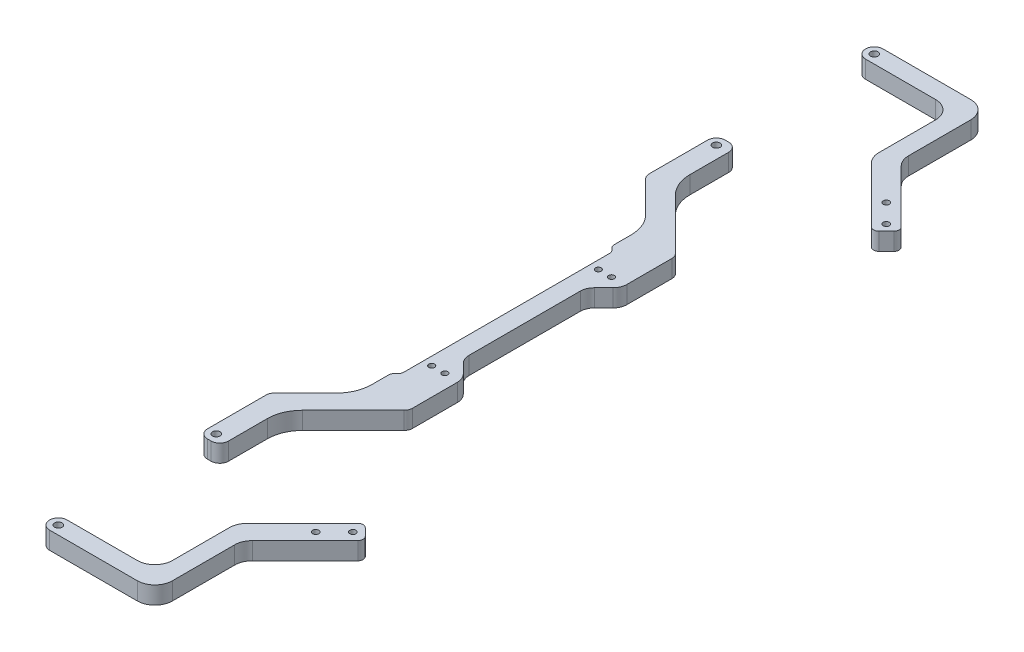
SolidWorks part; units mm, degrees
material "POM 乙缩醛共聚物"
ref_plane "前视基准面" through (0, 0, 0) normal (0, 0, 1) x (1, 0, 0)
ref_plane "上视基准面" through (0, 0, 0) normal (0, 1, 0) x (1, 0, 0)
ref_plane "右视基准面" through (0, 0, 0) normal (1, 0, 0) x (0, 0, -1)
sketch "草图1" plane through (0, 0, 0) normal (0, 1, 0) x (1, 0, 0)
  line L0 (-213.25, 0) -> (213.25, 0) construction
  line L1 (213.25, -47.5) -> (213.25, 47.5) construction
  line L2 (0, -213.25) -> (0, 213.25) construction
  line L3 (-213.25, -47.5) -> (-213.25, 47.5) construction
  line L4 (213.25, 0) -> (221.25, 0) construction
  line L5 (221.25, -67.5) -> (221.25, 67.5)
  line L6 (221.25, 67.5) -> (201.2006, 67.5)
  line L7 (0, 0) -> (180.3122, 180.3122) construction
  line L8 (201.2006, 67.5) -> (67.5, 201.2006)
  line L9 (67.5, 221.25) -> (67.5, 201.2006)
  line L10 (-67.5, 221.25) -> (67.5, 221.25)
  line L11 (-67.5, 221.25) -> (-67.5, 201.2006)
  line L12 (-201.2006, 67.5) -> (-67.5, 201.2006)
  line L13 (-221.25, 67.5) -> (-201.2006, 67.5)
  line L14 (-221.25, -67.5) -> (-221.25, 67.5)
  line L15 (221.25, -67.5) -> (201.2006, -67.5)
  line L16 (201.2006, -67.5) -> (67.5, -201.2006)
  line L17 (67.5, -221.25) -> (67.5, -201.2006)
  line L18 (-221.25, -67.5) -> (-201.2006, -67.5)
  line L19 (-201.2006, -67.5) -> (-67.5, -201.2006)
  line L20 (-67.5, -221.25) -> (-67.5, -201.2006)
  line L21 (-67.5, -221.25) -> (67.5, -221.25)
  circle A0 centre (0, 0) radius 100 construction
  circle A2 centre (0, 0) radius 110
  point P19 (134.3503, 134.3503)
  point P22 (0, 221.25)
  point P31 (-221.25, 0)
  dimension "D1" = 200
  dimension "D4" = 213.25
  dimension "D2" = 213.25
  dimension "D3" = 47.5
  dimension "D5" = 8
  dimension "D6" = 67.5
  dimension "D7" = 10
  dimension "D8" = 255
  dimension "D9" = 65
extrude "凸台-拉伸1" add sketch "草图1" along normal blind 3
sketch "草图2" plane through (0, 3, 0) normal (0, 1, 0) x (1, 0, 0)
  line L0 (0, 0) -> (0, -168) construction
  line L2 (-55, -70) -> (55, -70)
  line L3 (-55, -70) -> (-55, -168)
  line L4 (-55, -168) -> (55, -168)
  line L5 (55, -70) -> (55, -168)
  line L6 (-55, -70) -> (55, -168) construction
  line L7 (-55, -168) -> (55, -70) construction
  point P3 (0, -119)
  dimension "D1" = 168
  dimension "D2" = 110
  dimension "D3" = 98
extrude "切除-拉伸1" cut sketch "草图2" against normal blind 10
sketch "草图3" plane through (0, 3, 0) normal (0, 1, 0) x (1, 0, 0)
  line L0 (55, -168) -> (66, -168)
  line L1 (66, -168) -> (66, -78)
  line L2 (66, -78) -> (55, -78)
  line L3 (55, -78) -> (55, -168)
  dimension "D1" = 11
  dimension "D2" = 90
extrude "切除-拉伸2" cut sketch "草图3" against normal blind 10
sketch "草图4" plane through (0, 3, 0) normal (0, 1, 0) x (1, 0, 0)
  line L0 (-55, -168) -> (66, -168) construction
  line L1 (-4, -153) -> (24, -153)
  line L2 (-4, -153) -> (-4, -183)
  line L3 (-4, -183) -> (24, -183)
  line L4 (24, -153) -> (24, -183)
  line L5 (-4, -153) -> (24, -183) construction
  line L6 (-4, -183) -> (24, -153) construction
  line L7 (0, 0) -> (0, -232.4473) construction
  point P0 (10, -168)
  dimension "D1" = 10
  dimension "D2" = 28
  dimension "D3" = 30
extrude "切除-拉伸3" cut sketch "草图4" against normal blind 10
fillet "圆角1" radius 2 24 edges at (-4, 1.5, 183) (221.25, 1.5, -67.5) (221.25, 1.5, 67.5) (201.2006, 1.5, 67.5) (67.5, 1.5, 201.2006) (67.5, 1.5, 221.25) (-67.5, 1.5, 221.25) (-67.5, 1.5, 201.2006) (-201.2006, 1.5, 67.5) (-221.25, 1.5, 67.5) (-221.25, 1.5, -67.5) (-201.2006, 1.5, -67.5) (-67.5, 1.5, -201.2006) (-67.5, 1.5, -221.25) (67.5, 1.5, -221.25) (67.5, 1.5, -201.2006) (201.2006, 1.5, -67.5) (-55, 1.5, 95.2628) (-55, 1.5, 168) (66, 1.5, 88) (66, 1.5, 168) (-4, 1.5, 168) (24, 1.5, 168) (24, 1.5, 183)
sketch "草图5" plane through (0, 3, 0) normal (0, 1, 0) x (1, 0, 0)
  line L0 (0, 0) -> (-208.25, 0) construction
  line L1 (-208.25, -47.5) -> (-208.25, 47.5) construction
  line L2 (-208.25, 47.5) -> (-197.5, 47.5) construction
  line L3 (-197.5, 47.5) -> (-190, 47.5) construction
  line L4 (-197.5, -47.5) -> (-190, -47.5) construction
  line L5 (-208.25, -47.5) -> (-197.5, -47.5) construction
  line L6 (-47.5, 208.25) -> (47.5, 208.25) construction
  line L7 (0, 208.25) -> (0, 0) construction
  circle A0 centre (-208.25, 47.5) radius 2.65
  circle A1 centre (-197.5, 47.5) radius 1.65
  circle A2 centre (-190, 47.5) radius 1.65
  circle A3 centre (-190, -47.5) radius 1.65
  circle A4 centre (-197.5, -47.5) radius 1.65
  circle A5 centre (-208.25, -47.5) radius 2.65
  circle A24 centre (47.5, 190) radius 1.65
  circle A25 centre (47.5, 197.5) radius 1.65
  circle A26 centre (47.5, 208.25) radius 2.65
  circle A27 centre (-47.5, 208.25) radius 2.65
  circle A28 centre (-47.5, 197.5) radius 1.65
  circle A29 centre (-47.5, 190) radius 1.65
  circle A30 centre (190, -47.5) radius 1.65
  circle A31 centre (197.5, -47.5) radius 1.65
  circle A32 centre (208.25, -47.5) radius 2.65
  circle A33 centre (208.25, 47.5) radius 2.65
  circle A34 centre (197.5, 47.5) radius 1.65
  circle A35 centre (190, 47.5) radius 1.65
  circle A36 centre (-47.5, -190) radius 1.65
  circle A37 centre (-47.5, -197.5) radius 1.65
  circle A38 centre (-47.5, -208.25) radius 2.65
  circle A39 centre (47.5, -208.25) radius 2.65
  circle A40 centre (47.5, -197.5) radius 1.65
  circle A41 centre (47.5, -190) radius 1.65
  point P55 (1.5152, 1.5152)
  dimension "D2" = 5.3
  dimension "D4" = 7.5
  dimension "D5" = 3.3
  dimension "D7" = 95
  dimension "D1" = 208.25
  dimension "D3" = 10.75
  dimension "D6" = 4
extrude "切除-拉伸4" cut sketch "草图5" against normal blind 10
sketch "草图6" plane through (0, 3, 0) normal (0, 1, 0) x (1, 0, 0)
  line L0 (0, 0) -> (0, -221.25) construction
  line L1 (-65.5, -221.25) -> (65.5, -221.25) construction
  line L2 (67.5, -219.25) -> (67.5, -202.029) construction
  line L3 (-67.5, -237.25) -> (67.5, -237.25)
  line L4 (-67.5, -237.25) -> (-67.5, -205.25)
  line L5 (-67.5, -205.25) -> (67.5, -205.25)
  line L6 (67.5, -237.25) -> (67.5, -205.25)
  line L7 (-67.5, -237.25) -> (67.5, -205.25) construction
  line L8 (-67.5, -205.25) -> (67.5, -237.25) construction
  line L9 (-237.25, 67.5) -> (-237.25, -67.5)
  line L10 (-237.25, 67.5) -> (-205.25, 67.5)
  line L11 (-237.25, -67.5) -> (-205.25, -67.5)
  line L12 (-205.25, 67.5) -> (-205.25, -67.5)
  line L21 (-237.25, 67.5) -> (-205.25, -67.5) construction
  line L23 (67.5, 237.25) -> (-67.5, 237.25) [skipped]
  line L24 (67.5, 237.25) -> (67.5, 205.25) [skipped]
  line L25 (-67.5, 237.25) -> (-67.5, 205.25) [skipped]
  line L26 (67.5, 205.25) -> (-67.5, 205.25) [skipped]
  line L27 (237.25, -67.5) -> (237.25, 67.5) [skipped]
  line L28 (237.25, -67.5) -> (205.25, -67.5) [skipped]
  line L29 (237.25, 67.5) -> (205.25, 67.5) [skipped]
  line L30 (205.25, -67.5) -> (205.25, 67.5) [skipped]
  line L34 (237.25, 67.5) -> (205.25, 67.5)
  line L35 (205.25, 67.5) -> (205.25, -67.5)
  line L36 (237.25, -67.5) -> (205.25, -67.5)
  line L37 (237.25, 67.5) -> (237.25, -67.5)
  line L38 (-221.25, 0) -> (0, 0) construction
  line L39 (-219.5626, -92.2876) -> (-219.5626, -92.9346) construction
  line L40 (-67.5, 205.25) -> (67.5, 205.25)
  line L41 (-205.25, 67.5) -> (-237.25, -67.5) construction
  line L42 (67.5, 237.25) -> (67.5, 205.25)
  line L43 (-67.5, 237.25) -> (67.5, 237.25)
  line L44 (-67.5, 237.25) -> (-67.5, 205.25)
  point P26 (0, 0)
  dimension "D1" = 16
  dimension "D2" = 4
extrude "切除-拉伸5" cut sketch "草图6" against normal through all
sketch "草图7" plane through (0, 3, 0) normal (0, 1, 0) x (1, 0, 0)
  line L0 (0, 0) -> (169.5, 0) construction
  line L3 (140.5, 65) -> (169.5, 65)
  line L4 (140.5, 65) -> (140.5, -65)
  line L5 (140.5, -65) -> (169.5, -65)
  line L6 (169.5, 65) -> (169.5, -65)
  line L7 (140.5, 65) -> (169.5, -65) construction
  line L8 (140.5, -65) -> (169.5, 65) construction
  point P5 (155, 0)
  dimension "D1" = 130
  dimension "D2" = 29
  dimension "D3" = 155
extrude "切除-拉伸6" cut sketch "草图7" against normal blind 10
sketch "草图8" plane through (0, 3, 0) normal (0, 1, 0) x (1, 0, 0)
  line L0 (0, 0) -> (134.3503, -134.3503) construction
  line L1 (68.0858, -200.6148) -> (200.6148, -68.0858) construction
  line L2 (134.3503, -134.3503) -> (162.6346, -162.6346) construction
  line L3 (110.6622, -214.6069) -> (214.6069, -110.6622)
  line L4 (214.6069, -110.6622) -> (199.5118, -69.1888)
  line L5 (110.6622, -214.6069) -> (69.1888, -199.5118)
  line L6 (199.5118, -69.1888) -> (69.1888, -199.5118)
  line L7 (0, 0) -> (252.2182, 0) construction
  line L8 (0, 0) -> (0, -92.3729) construction
  line L9 (214.6069, 110.6622) -> (199.5118, 69.1888)
  line L10 (110.6622, 214.6069) -> (214.6069, 110.6622)
  line L11 (110.6622, 214.6069) -> (69.1888, 199.5118)
  line L12 (199.5118, 69.1888) -> (69.1888, 199.5118)
  line L13 (-214.6069, -110.6622) -> (-199.5118, -69.1888)
  line L14 (-110.6622, -214.6069) -> (-214.6069, -110.6622)
  line L15 (-110.6622, -214.6069) -> (-69.1888, -199.5118)
  line L16 (-199.5118, -69.1888) -> (-69.1888, -199.5118)
  line L17 (-110.6622, 214.6069) -> (-214.6069, 110.6622)
  line L18 (-110.6622, 214.6069) -> (-69.1888, 199.5118)
  line L19 (-199.5118, 69.1888) -> (-69.1888, 199.5118)
  line L20 (-214.6069, 110.6622) -> (-199.5118, 69.1888)
  dimension "D1" = 40
  dimension "D2" = 73.5
  dimension "D3" = 115
extrude "凸台-拉伸2" add sketch "草图8" against normal up to surface (3 mm away) up to face at (155, 0, 0)
ref_plane "基准面1" through (0, 0, 0) normal (-0.7071, 0, 0.7071) x (0.7071, 0, 0.7071)
sketch "草图12" plane through (0, 3, 0) normal (0, 1, 0) x (1, 0, 0)
  line L0 (0, 0) -> (162.6346, -162.6346) construction
  line L1 (110.6622, -214.6069) -> (214.6069, -110.6622) construction
  line L2 (155.5635, -155.5635) -> (162.6346, -148.4924) construction
  line L3 (162.6346, -148.4924) -> (152.028, -137.8858) construction
  line L4 (0, 0) -> (24.1105, 24.1105) construction
  line L5 (0, 0) -> (252.2182, 0) construction
  line L6 (162.6346, 148.4924) -> (152.028, 137.8858) construction
  line L7 (252.2182, -23.8295) -> (253.2892, -23.8295) construction
  line L8 (0, 0) -> (0, 85.4115) construction
  line L9 (155.5635, 155.5635) -> (162.6346, 148.4924) construction
  line L10 (-162.6346, -148.4924) -> (-152.028, -137.8858) construction
  line L11 (-155.5635, -155.5635) -> (-162.6346, -148.4924) construction
  line L12 (0, 0) -> (-162.6346, -162.6346) construction
  line L13 (-155.5635, 155.5635) -> (-162.6346, 148.4924) construction
  line L14 (-162.6346, 148.4924) -> (-152.028, 137.8858) construction
  circle A0 centre (162.6346, -148.4924) radius 1.65
  circle A1 centre (152.028, -137.8858) radius 1.65
  circle A2 centre (137.8858, -152.028) radius 1.65
  circle A3 centre (148.4924, -162.6346) radius 1.65
  circle A4 centre (148.4924, 162.6346) radius 1.65
  circle A5 centre (137.8858, 152.028) radius 1.65
  circle A6 centre (152.028, 137.8858) radius 1.65
  circle A7 centre (162.6346, 148.4924) radius 1.65
  circle A8 centre (-148.4924, -162.6346) radius 1.65
  circle A9 centre (-137.8858, -152.028) radius 1.65
  circle A10 centre (-152.028, -137.8858) radius 1.65
  circle A11 centre (-162.6346, -148.4924) radius 1.65
  circle A12 centre (-162.6346, 148.4924) radius 1.65
  circle A13 centre (-152.028, 137.8858) radius 1.65
  circle A14 centre (-137.8858, 152.028) radius 1.65
  circle A15 centre (-148.4924, 162.6346) radius 1.65
  dimension "D1" = 3.3
  dimension "D2" = 3.3
  dimension "D3" = 15
  dimension "D4" = 20
  dimension "D5" = 205
extrude "切除-拉伸7" cut sketch "草图12" against normal blind 112
sketch "草图13" plane through (0, 3, 0) normal (0, 1, 0) x (1, 0, 0)
  line L0 (-205.25, 0) -> (205.25, 0)
  line L1 (-205.25, -67.5) -> (-205.25, 67.5) construction
  line L2 (205.25, 67.5) -> (205.25, -67.5) construction
extrude "切除-拉伸-薄壁1" cut sketch "草图13" against normal through all both and the other way through all thin thin type mid plane wall 2
sketch "草图14" plane through (0, 3, 0) normal (0, 1, 0) x (1, 0, 0)
  line L0 (0, 205.25) -> (0, -205.25)
  line L1 (-67.5, 205.25) -> (67.5, 205.25) construction
  line L2 (67.5, -205.25) -> (-67.5, -205.25) construction
extrude "切除-拉伸-薄壁2" cut sketch "草图14" against normal through all and the other way through all thin thin type mid plane wall 2
fillet "圆角2" radius 3 8 edges at (-1, 1.5, 205.25) (-69.1888, 1.5, 199.5118) (-67.5, 1.5, 205.25) (-205.25, 1.5, 1) (-199.5118, 1.5, 69.1888) (-205.25, 1.5, 67.5) (-214.6069, 1.5, 110.6622) (-110.6622, 1.5, 214.6069)
fillet "圆角3" radius 3 14 edges at (169.5, 1.5, 65) (140.5, 1.5, 65) (109.9955, 1.5, 1) (140.5, 1.5, 1) (169.5, 1.5, 1) (205.25, 1.5, 1) (205.25, 1.5, 67.5) (199.5118, 1.5, 69.1888) (214.6069, 1.5, 110.6622) (110.6622, 1.5, 214.6069) (69.1888, 1.5, 199.5118) (67.5, 1.5, 205.25) (1, 1.5, 183) (1, 1.5, 205.25)
fillet "圆角4" radius 3 13 edges at (1, 1.5, -109.9955) (1, 1.5, -205.25) (69.1888, 1.5, -199.5118) (67.5, 1.5, -205.25) (110.6622, 1.5, -214.6069) (214.6069, 1.5, -110.6622) (205.25, 1.5, -67.5) (169.5, 1.5, -65) (140.5, 1.5, -65) (109.9955, 1.5, -1) (140.5, 1.5, -1) (169.5, 1.5, -1) (205.25, 1.5, -1)
fillet "圆角5" radius 3 10 edges at (-67.5, 1.5, -205.25) (-69.1888, 1.5, -199.5118) (-110.6622, 1.5, -214.6069) (-214.6069, 1.5, -110.6622) (-199.5118, 1.5, -69.1888) (-205.25, 1.5, -67.5) (-205.25, 1.5, -1) (-109.9955, 1.5, -1) (-1, 1.5, -109.9955) (-1, 1.5, -205.25)
fillet "圆角6" radius 3 2 edges at (-1, 1.5, 183) (-109.9955, 1.5, 1)
sketch "草图15" plane through (0, 0, 0) normal (0, -1, 0) x (1, 0, 0)
  line L0 (148.4924, -162.6346) -> (106.066, -205.061) construction
  line L1 (162.6346, -162.6346) -> (105.0927, -105.0927) construction
  line L2 (112.0136, -213.2555) -> (213.2555, -112.0136) construction
  line L3 (162.6346, -162.6346) -> (213.2555, -112.0136) construction
  line L4 (106.066, -205.061) -> (91.9239, -190.9188) construction
  line L5 (205.061, -106.066) -> (190.9188, -91.9239) construction
  line L6 (162.6346, -148.4924) -> (205.061, -106.066) construction
  line L7 (0, 0) -> (248.6294, 0) construction
  line L8 (0, 0) -> (0, -244.0653) construction
  line L9 (-162.6346, -148.4924) -> (-205.061, -106.066) construction
  line L10 (-205.061, -106.066) -> (-190.9188, -91.9239) construction
  line L11 (-106.066, -205.061) -> (-91.9239, -190.9188) construction
  line L12 (-162.6346, -162.6346) -> (-213.2555, -112.0136) construction
  line L13 (-162.6346, -162.6346) -> (-105.0927, -105.0927) construction
  line L14 (-148.4924, -162.6346) -> (-106.066, -205.061) construction
  line L15 (-148.4924, 162.6346) -> (-106.066, 205.061) construction
  line L16 (-162.6346, 162.6346) -> (-105.0927, 105.0927) construction
  line L17 (-162.6346, 162.6346) -> (-213.2555, 112.0136) construction
  line L18 (-106.066, 205.061) -> (-91.9239, 190.9188) construction
  line L19 (-205.061, 106.066) -> (-190.9188, 91.9239) construction
  line L20 (-162.6346, 148.4924) -> (-205.061, 106.066) construction
  line L21 (162.6346, 148.4924) -> (205.061, 106.066) construction
  line L22 (205.061, 106.066) -> (190.9188, 91.9239) construction
  line L23 (106.066, 205.061) -> (91.9239, 190.9188) construction
  line L24 (162.6346, 162.6346) -> (213.2555, 112.0136) construction
  line L25 (162.6346, 162.6346) -> (105.0927, 105.0927) construction
  line L26 (148.4924, 162.6346) -> (106.066, 205.061) construction
  circle A0 centre (106.066, -205.061) radius 1.75
  circle A1 centre (91.9239, -190.9188) radius 1.75
  circle A2 centre (190.9188, -91.9239) radius 1.75
  circle A3 centre (205.061, -106.066) radius 1.75
  circle A4 centre (-205.061, -106.066) radius 1.75
  circle A5 centre (-190.9188, -91.9239) radius 1.75
  circle A6 centre (-91.9239, -190.9188) radius 1.75
  circle A7 centre (-106.066, -205.061) radius 1.75
  circle A8 centre (-106.066, 205.061) radius 1.75
  circle A9 centre (-91.9239, 190.9188) radius 1.75
  circle A10 centre (-190.9188, 91.9239) radius 1.75
  circle A11 centre (-205.061, 106.066) radius 1.75
  circle A12 centre (205.061, 106.066) radius 1.75
  circle A13 centre (190.9188, 91.9239) radius 1.75
  circle A14 centre (91.9239, 190.9188) radius 1.75
  circle A15 centre (106.066, 205.061) radius 1.75
  dimension "D2" = 3.5
  dimension "D4" = 3.5
  dimension "D1" = 140
  dimension "D3" = 20
extrude "切除-拉伸8" cut sketch "草图15" against normal blind 10
sketch "草图16" plane through (0, 3, 0) normal (0, 1, 0) x (1, 0, 0)
  line L0 (0, 0) -> (-162.6346, 162.6346) construction
  line L1 (-112.0136, 213.2555) -> (-213.2555, 112.0136) construction
  line L2 (-134.3503, 134.3503) -> (-118.7939, 149.9066) construction
  line L3 (-94.7523, 94.7523) -> (-71.7713, 117.7333) construction
  circle A0 centre (-118.7939, 149.9066) radius 1.65
  circle A1 centre (-71.7713, 117.7333) radius 2.15
  circle A2 centre (-117.7333, 71.7713) radius 2.15
  circle A3 centre (-149.9066, 118.7939) radius 1.65
  dimension "D3" = 3.3
  dimension "D4" = 4.3
  dimension "D5" = 65
  dimension "D6" = 56
  dimension "D1" = 22
  dimension "D2" = 190
extrude "切除-拉伸9" cut sketch "草图16" against normal blind 10
sketch "草图18" plane through (0, 3, 0) normal (0, 1, 0) x (1, 0, 0)
  line L0 (0, 0) -> (-264.5947, 0) construction
  line L1 (-268.4627, 195) -> (-239.3639, 195) construction
  line L2 (-182, -75.934) -> (-182, 75.934)
  line L3 (-182, 75.934) -> (-218.25, 112.184)
  line L4 (-218.25, 112.184) -> (-218.25, 188.3799)
  line L5 (-205.25, 4) -> (-205.25, 64.5) construction
  line L6 (0, 0) -> (-162.6346, 162.6346) construction
  line L7 (-112.0136, 213.2555) -> (-213.2555, 112.0136) construction
  line L8 (-213.1287, 190.5013) -> (-152.7351, 130.1076)
  line L9 (-205.25, -82.2134) -> (-205.25, 82.2134)
  line L10 (-205.25, 82.2134) -> (-230.25, 107.2134)
  line L11 (-230.25, 107.2134) -> (-230.25, 212.5221)
  line L12 (-221.7145, 216.0576) -> (-144.2498, 138.5929)
  line L13 (-144.2498, 138.5929) -> (-152.7351, 130.1076)
  line L15 (-268.4627, -195) -> (-227.2747, -195) construction
  line L16 (-144.2498, -138.5929) -> (-152.7351, -130.1076)
  line L17 (-221.7145, -216.0576) -> (-144.2498, -138.5929)
  line L18 (-230.25, -107.2134) -> (-230.25, -212.5221)
  line L19 (-205.25, -82.2134) -> (-230.25, -107.2134)
  line L20 (-213.1287, -190.5013) -> (-152.7351, -130.1076)
  line L21 (-218.25, -112.184) -> (-218.25, -188.3799)
  line L22 (-182, -75.934) -> (-218.25, -112.184)
  line L23 (-148.4924, 134.3503) -> (-152.028, 137.8858) construction
  circle A0 centre (-190, 47.5) radius 1.65 construction
  circle A1 centre (-197.5, 47.5) radius 1.65 construction
  circle A2 centre (-197.5, -47.5) radius 1.65 construction
  circle A3 centre (-190, -47.5) radius 1.65 construction
  circle A4 centre (-190, 47.5) radius 1.65
  circle A5 centre (-197.5, 47.5) radius 1.65
  circle A6 centre (-197.5, -47.5) radius 1.65
  circle A7 centre (-190, -47.5) radius 1.65
  circle A8 centre (-190.9188, 91.9239) radius 1.75 construction
  arc A9 (-230.25, 212.5221) -> (-221.7145, 216.0576) centre (-225.25, 212.5221) cw
  arc A11 (-218.25, 188.3799) -> (-213.1287, 190.5013) centre (-215.25, 188.3799) cw
  circle A12 centre (-152.028, 137.8858) radius 1.65 construction
  arc A13 (-218.25, -188.3799) -> (-213.1287, -190.5013) centre (-215.25, -188.3799) ccw
  arc A14 (-230.25, -212.5221) -> (-221.7145, -216.0576) centre (-225.25, -212.5221) ccw
  circle A15 centre (-197.5, -47.5) radius 1.65
  circle A16 centre (-190, -47.5) radius 1.65
  circle A24 centre (-152.028, -137.8858) radius 1.65
  circle A25 centre (-162.6346, -148.4924) radius 1.65
  circle A28 centre (-152.028, -137.8858) radius 1.65 construction
  circle A30 centre (-152.028, 137.8858) radius 1.65
  circle A31 centre (-162.6346, -148.4924) radius 1.65 construction
  circle A32 centre (-162.6346, 148.4924) radius 1.65
  point P58 (-205.25, 0)
  point P60 (-182, 0)
  dimension "D3" = 8
  dimension "D9" = 5
  dimension "D10" = 3
  dimension "D11" = 5
  dimension "D1" = 195
  dimension "D2" = 13
  dimension "D4" = 5
  dimension "D6" = 12
  dimension "D7" = 12
  dimension "D8" = 12
extrude "凸台-拉伸3" add sketch "草图18" along normal blind 10
sketch "草图19" plane through (-205.25, 0, 0) normal (-1, 0, 0) x (0, 0, 1)
  line L0 (-245.4596, 3) -> (284.5404, 3)
  line L1 (159.8061, 3) -> (213.2555, 3) construction
  line L2 (284.5404, 3) -> (284.5404, -37)
  line L3 (284.5404, -37) -> (-245.4596, -37)
  line L4 (-245.4596, -37) -> (-245.4596, 3)
  dimension "D1" = 40
  dimension "D2" = 530
  dimension "D3" = 246.4596
extrude "切除-拉伸10" cut sketch "草图19" against normal through all both and the other way through all
sketch "草图20" plane through (0, 13, 0) normal (0, 1, 0) x (1, 0, 0)
  circle A0 centre (-152.028, 137.8858) radius 1.65 construction
  circle A1 centre (-162.6346, 148.4924) radius 1.65 construction
  circle A2 centre (-152.028, 137.8858) radius 1.65
  circle A3 centre (-162.6346, 148.4924) radius 1.65
extrude "凸台-拉伸4" add sketch "草图20" against normal up to surface (10 mm away) up to face at (-201.7968, 3, 0)
sketch "草图23" plane through (0, 13, 0) normal (0, 1, 0) x (1, 0, 0)
  line L0 (-225.25, 217.5221) -> (-175.25, 217.5221)
  line L1 (-165.25, 207.5221) -> (-165.25, 159.5931)
  line L2 (-221.7145, 216.0576) -> (-144.2498, 138.5929) construction
  line L3 (-175.25, 169.5931) -> (-175.25, 197.5221)
  line L4 (-185.25, 207.5221) -> (-213.1789, 207.5221)
  line L5 (-221.7145, 216.0576) -> (-213.1789, 207.5221)
  line L6 (-175.25, 169.5931) -> (-165.25, 159.5931)
  line L7 (-175.25, 169.5931) -> (-144.2498, 138.5929)
  arc A0 (-221.7145, 216.0576) -> (-230.25, 212.5221) centre (-225.25, 212.5221) ccw construction
  arc A1 (-221.7145, 216.0576) -> (-225.25, 217.5221) centre (-225.25, 212.5221) ccw
  arc A2 (-175.25, 217.5221) -> (-165.25, 207.5221) centre (-175.25, 207.5221) cw
  arc A3 (-175.25, 197.5221) -> (-185.25, 207.5221) centre (-185.25, 197.5221) ccw
  point P10 (-165.25, 217.5221)
  line M27 (-144.2498, 138.5929) -> (-221.7145, 216.0576)
  arc M28 (-221.7145, 216.0576) -> (-230.25, 212.5221) centre (-225.25, 212.5221) ccw
  dimension "D4" = 10
  dimension "D1" = 10
  dimension "D2" = 60
  dimension "D3" = 10
extrude "凸台-拉伸6" add sketch "草图23" against normal blind 10 contours A3 L3 L1 A2 L0 L4 M27 M28
sketch "草图24" plane through (0, 3, 0) normal (0, -1, 0) x (1, 0, 0)
  line L0 (-218.25, -188.3799) -> (-218.25, -207.5221)
  line L1 (-218.25, -207.5221) -> (-213.1789, -207.5221)
  line L2 (-213.1789, -207.5221) -> (-175.25, -169.5931)
  line L3 (-175.25, -169.5931) -> (-175.25, -152.6226)
  line L4 (-213.1287, -190.5013) -> (-152.7351, -130.1076) construction
  line L5 (-175.25, -152.6226) -> (-218.25, -188.3799)
  line L6 (-185.25, -207.5221) -> (-213.1789, -207.5221) construction
extrude "切除-拉伸12" cut sketch "草图24" against normal through all
mirror "镜向1" about plane through (0, 0, 0) normal (0, 0, 1) of "切除-拉伸12", "凸台-拉伸6"
fillet "圆角7" radius 5 2 edges at (-218.25, 8, -207.5221) (-218.25, 8, 207.5221)
fillet "圆角8" radius 5 10 edges at (-152.7351, 8, 130.1076) (-144.2498, 8, 138.5929) (-230.25, 8, 107.2134) (-230.25, 8, -107.2134) (-144.2498, 8, -138.5929) (-152.7351, 8, -130.1076) (-182, 8, -75.934) (-182, 8, 75.934) (-175.25, 8, 152.6226) (-175.25, 8, -152.6226)
sketch "草图25" plane through (0, 13, 0) normal (0, 1, 0) x (1, 0, 0)
  line L0 (0, 0) -> (-287.1356, 0) construction
  circle A0 centre (-152.028, 137.8858) radius 1.65
  circle A1 centre (-162.6346, 148.4924) radius 1.65
  circle A2 centre (-152.028, -137.8858) radius 1.65 construction
  circle A3 centre (-162.6346, -148.4924) radius 1.65 construction
extrude "切除-拉伸13" cut sketch "草图25" against normal through all
sketch "草图26" plane through (0, 13, 0) normal (0, 1, 0) x (1, 0, 0)
  line L0 (0, 0) -> (-220.6337, 0) construction
  line L1 (0, 0) -> (-174.267, 174.267) construction
  line L2 (-152.028, 137.8858) -> (-144.9569, 144.9569) construction
  line L3 (-144.9569, 144.9569) -> (-137.8858, 152.028) construction
  line L4 (-137.8858, 152.028) -> (-148.4924, 162.6346) construction
  line L5 (-140.7142, 146.3711) -> (-165.25, 170.9069)
  line L6 (-165.25, 207.5221) -> (-165.25, 159.5931) construction
  line L7 (-136.4716, 146.3711) -> (-132.229, 150.6137)
  line L8 (-132.229, 154.8564) -> (-165.25, 187.8774)
  line L9 (-165.25, 159.5931) -> (-147.7853, 142.1285) construction
  line L10 (-173.7855, 151.1581) -> (-156.2706, 133.6432) construction
  line L11 (-165.25, 187.8774) -> (-165.25, 170.9069)
  line L12 (-132.229, -154.8564) -> (-165.25, -187.8774)
  line L13 (-136.4716, -146.3711) -> (-132.229, -150.6137)
  line L14 (-140.7142, -146.3711) -> (-165.25, -170.9069)
  line L15 (-165.25, -187.8774) -> (-165.25, -170.9069)
  line L16 (-137.8858, -152.028) -> (-148.4924, -162.6346) construction
  line L17 (-144.9569, -144.9569) -> (-137.8858, -152.028) construction
  circle A0 centre (-137.8858, 152.028) radius 1.75
  circle A1 centre (-148.4924, 162.6346) radius 1.75
  arc A2 (-132.229, 150.6137) -> (-132.229, 154.8564) centre (-134.3503, 152.7351) ccw
  arc A3 (-140.7142, 146.3711) -> (-136.4716, 146.3711) centre (-138.5929, 148.4924) ccw
  arc A4 (-132.229, -150.6137) -> (-132.229, -154.8564) centre (-134.3503, -152.7351) cw
  arc A5 (-140.7142, -146.3711) -> (-136.4716, -146.3711) centre (-138.5929, -148.4924) cw
  circle A6 centre (-148.4924, -162.6346) radius 1.75
  circle A7 centre (-137.8858, -152.028) radius 1.75
  dimension "D3" = 3.5
  dimension "D5" = 3.5
  dimension "D7" = 3
  dimension "D1" = 45
  dimension "D2" = 10
  dimension "D4" = 15
  dimension "D6" = 5
extrude "凸台-拉伸7" add sketch "草图26" against normal up to surface (10 mm away) up to face at (-152.028, 3, -136.2358)
sketch "草图27" plane through (0, 13, 0) normal (0, 1, 0) x (1, 0, 0)
  line L0 (0, 0) -> (-205.25, 0) construction
  line L1 (-205.25, -82.2134) -> (-205.25, 82.2134) construction
  line L2 (-165.25, 170.9069) -> (-175.25, 180.9069)
  line L3 (-175.25, 154.6937) -> (-175.25, 197.5221) construction
  line L4 (-175.25, 180.9069) -> (-175.25, 129.5435)
  line L5 (-175.25, 129.5435) -> (-140.7781, 129.5435)
  line L6 (-140.7781, 129.5435) -> (-140.7142, 146.3711)
  line L7 (-140.7142, 146.3711) -> (-165.25, 170.9069)
  line L8 (-140.7142, -146.3711) -> (-165.25, -170.9069)
  line L9 (-140.7781, -129.5435) -> (-140.7142, -146.3711)
  line L10 (-175.25, -129.5435) -> (-140.7781, -129.5435)
  line L11 (-175.25, -180.9069) -> (-175.25, -129.5435)
  line L12 (-165.25, -170.9069) -> (-175.25, -180.9069)
  dimension "D1" = 16.8276
  dimension "D2" = 34.4719
extrude "切除-拉伸14" cut sketch "草图27" against normal blind 10
fillet "圆角9" radius 10 4 edges at (-165.25, 8, 187.8774) (-175.25, 8, 180.9069) (-165.25, 8, -187.8774) (-175.25, 8, -180.9069)
fillet "圆角13" radius 20 2 edges at (-218.25, 8, 112.184) (-205.25, 8, 82.2134)
fillet "圆角14" radius 20 2 edges at (-218.25, 8, -112.184) (-205.25, 8, -82.2134)
sketch "草图30" plane through (0, 3, 0) normal (0, -1, 0) x (1, 0, 0)
  line L0 (-205.25, 0) -> (-173.7724, 0) construction
  line L1 (-205.25, 73.9291) -> (-205.25, -73.9291) construction
  line L2 (-182, 45) -> (-192, 35)
  line L3 (-182, 73.8629) -> (-182, -73.8629) construction
  line L4 (-192, 35) -> (-192, -35)
  line L5 (-182, 45) -> (-182, -45)
  line L6 (-182, -45) -> (-192, -35)
  point P12 (-182, 0)
  point P13 (-192, 0)
  dimension "D1" = 45
  dimension "D2" = 35
  dimension "D3" = 10
extrude "切除-拉伸16" cut sketch "草图30" against normal through all
fillet "圆角15" radius 8 4 edges at (-182, 8, 45) (-182, 8, -45) (-192, 8, -35) (-192, 8, 35)
sketch "草图31" plane through (0, 3, 0) normal (0, -1, 0) x (1, 0, 0)
  line L0 (-205.25, 0) -> (-236.4193, 0) construction
  line L1 (-205.25, 73.9291) -> (-205.25, -73.9291) construction
  line L2 (-205.25, 63) -> (-202.25, 60)
  line L3 (-202.25, 60) -> (-202.25, 0)
  line L4 (-205.25, 63) -> (-205.25, -63)
  line L5 (-205.25, -63) -> (-202.25, -60)
  line L6 (-202.25, -60) -> (-202.25, 0)
  dimension "D1" = 135
  dimension "D2" = 60
  dimension "D3" = 3
extrude "切除-拉伸17" cut sketch "草图31" against normal through all
fillet "圆角16" radius 3 4 edges at (-205.25, 8, -63) (-205.25, 8, 63) (-202.25, 8, 60) (-202.25, 8, -60)
sketch "草图32" plane through (0, 3, 0) normal (0, -1, 0) x (1, 0, 0)
  line L0 (0, 0) -> (-270.1642, 0) construction
  line L1 (-213.25, 207.5221) -> (-230.25, 207.5221)
  line L2 (-230.25, 109.2845) -> (-230.25, 212.5221) construction
  line L3 (-213.25, 207.5221) -> (-213.25, 147.5221)
  line L4 (-213.25, 147.5221) -> (-230.25, 147.5221)
  line L5 (-230.25, 207.5221) -> (-230.25, 147.5221)
  line L6 (-230.25, -207.5221) -> (-230.25, -147.5221)
  line L7 (-213.25, -147.5221) -> (-230.25, -147.5221)
  line L8 (-213.25, -207.5221) -> (-213.25, -147.5221)
  line L9 (-213.25, -207.5221) -> (-230.25, -207.5221)
  dimension "D1" = 60
extrude "切除-拉伸18" cut sketch "草图32" against normal through all
fillet "圆角17" radius 5 3 edges at (-230.25, 13, 210.0221) (-230.25, 8, 207.5221) (-230.25, 3, 210.0221)
fillet "圆角18" radius 5 4 edges at (-230.25, 8, 147.5221) (-230.25, 8, -147.5221) (-218.25, 8, -147.5221) (-218.25, 8, 147.5221)
fillet "圆角19" radius 5 1 edges at (-230.25, 8, -207.5221)
sketch "草图33" plane through (0, 13, 0) normal (0, 1, 0) x (1, 0, 0)
  line L0 (-225.25, -212.5221) -> (-225.25, 228.6741) construction
  line L1 (-192, 0) -> (-297.6492, 0) construction
  line L2 (-192, -31.6863) -> (-192, 31.6863) construction
  circle A0 centre (-225.25, -212.5221) radius 2.15
  circle A1 centre (-225.25, -142.5221) radius 2.15
  circle A2 centre (-225.25, 212.5221) radius 2.15
  circle A3 centre (-225.25, 142.5221) radius 2.15
  dimension "D1" = 4.3
  dimension "D2" = 70
extrude "切除-拉伸19" cut sketch "草图33" against normal through all
sketch "草图34" plane through (0, 13, 0) normal (0, 1, 0) x (1, 0, 0)
  line L0 (-225.25, 212.5221) -> (-174.3723, 212.5221) construction
  line L1 (-175.25, 192.0196) -> (-165.25, 192.0196)
  line L2 (0, 0) -> (-388.6241, 0) construction
  line L3 (-175.25, -217.5221) -> (-225.25, -217.5221) construction
  line L4 (-225.25, -207.5221) -> (-185.25, -207.5221) construction
  line L5 (-225.25, -232.5221) -> (-174.3723, -232.5221) construction
  line L6 (-225.25, -212.5221) -> (-174.3723, -212.5221) construction
  line L7 (-165.25, -192.0196) -> (-165.25, -227.5221)
  line L8 (-225.25, 232.5221) -> (-174.3723, 232.5221) construction
  line L9 (-175.25, 237.5221) -> (-225.25, 237.5221)
  line L10 (-225.25, 227.5221) -> (-185.25, 227.5221)
  line L11 (-225.25, 227.5221) -> (-185.25, 227.5221) construction
  line L12 (-136.4716, -146.3711) -> (-132.229, -150.6137)
  line L13 (-175.25, -217.5221) -> (-175.25, -192.0196)
  line L14 (-225.25, -227.5221) -> (-185.25, -227.5221)
  line L15 (-175.25, -237.5221) -> (-225.25, -237.5221)
  line L16 (-225.25, 207.5221) -> (-185.25, 207.5221)
  line L17 (-175.25, 197.5221) -> (-175.25, 185.049)
  line L18 (-172.3211, 177.9779) -> (-140.7142, 146.3711)
  line L19 (-136.4716, 146.3711) -> (-132.229, 150.6137)
  line L20 (-132.229, 154.8564) -> (-162.3211, 184.9485)
  line L21 (-165.25, 192.0196) -> (-165.25, 207.5221)
  line L22 (-175.25, 217.5221) -> (-225.25, 217.5221)
  line L23 (-225.25, 207.5221) -> (-185.25, 207.5221) construction
  line L24 (-175.25, 217.5221) -> (-175.25, 192.0196)
  line L26 (-136.4716, 146.3711) -> (-132.229, 150.6137)
  line L28 (-165.25, 192.0196) -> (-165.25, 227.5221)
  line L29 (-175.25, 217.5221) -> (-225.25, 217.5221) construction
  line L30 (-175.25, -192.0196) -> (-165.25, -192.0196)
  arc A2 (-175.25, 237.5221) -> (-165.25, 227.5221) centre (-175.25, 227.5221) cw
  circle A4 centre (-225.25, 232.5221) radius 2.15
  arc A5 (-185.25, 227.5221) -> (-175.25, 217.5221) centre (-185.25, 217.5221) cw
  arc A6 (-165.25, -207.5221) -> (-175.25, -217.5221) centre (-175.25, -207.5221) cw construction
  arc A7 (-175.25, -197.5221) -> (-185.25, -207.5221) centre (-185.25, -197.5221) cw construction
  arc A8 (-230.25, -212.5221) -> (-225.25, -207.5221) centre (-225.25, -212.5221) cw construction
  arc A9 (-225.25, 237.5221) -> (-225.25, 227.5221) centre (-225.25, 232.5221) ccw
  arc A10 (-225.25, -217.5221) -> (-230.25, -212.5221) centre (-225.25, -212.5221) cw construction
  arc A11 (-132.229, -150.6137) -> (-132.229, -154.8564) centre (-134.3503, -152.7351) cw
  arc A12 (-140.7142, -146.3711) -> (-136.4716, -146.3711) centre (-138.5929, -148.4924) cw
  arc A13 (-225.25, -237.5221) -> (-225.25, -227.5221) centre (-225.25, -232.5221) cw
  arc A14 (-185.25, -227.5221) -> (-175.25, -217.5221) centre (-185.25, -217.5221) ccw
  circle A15 centre (-225.25, -232.5221) radius 2.15
  arc A16 (-225.25, 217.5221) -> (-230.25, 212.5221) centre (-225.25, 212.5221) ccw
  arc A17 (-230.25, 212.5221) -> (-225.25, 207.5221) centre (-225.25, 212.5221) ccw
  arc A18 (-175.25, 197.5221) -> (-185.25, 207.5221) centre (-185.25, 197.5221) ccw
  arc A19 (-175.25, 185.049) -> (-172.3211, 177.9779) centre (-165.25, 185.049) ccw
  arc A20 (-140.7142, 146.3711) -> (-136.4716, 146.3711) centre (-138.5929, 148.4924) ccw
  arc A21 (-132.229, 150.6137) -> (-132.229, 154.8564) centre (-134.3503, 152.7351) ccw
  arc A22 (-165.25, 192.0196) -> (-162.3211, 184.9485) centre (-155.25, 192.0196) ccw
  arc A23 (-165.25, 207.5221) -> (-175.25, 217.5221) centre (-175.25, 207.5221) ccw
  arc A24 (-225.25, 217.5221) -> (-230.25, 212.5221) centre (-225.25, 212.5221) ccw construction
  arc A25 (-230.25, 212.5221) -> (-225.25, 207.5221) centre (-225.25, 212.5221) ccw construction
  arc A26 (-175.25, 197.5221) -> (-185.25, 207.5221) centre (-185.25, 197.5221) ccw construction
  arc A28 (-140.7142, 146.3711) -> (-136.4716, 146.3711) centre (-138.5929, 148.4924) ccw
  arc A29 (-132.229, 150.6137) -> (-132.229, 154.8564) centre (-134.3503, 152.7351) ccw
  arc A31 (-165.25, 207.5221) -> (-175.25, 217.5221) centre (-175.25, 207.5221) ccw construction
  arc A32 (-175.25, -237.5221) -> (-165.25, -227.5221) centre (-175.25, -227.5221) ccw
  dimension "D3" = 4.3
  dimension "D4" = 10
  dimension "D2" = 0
extrude "凸台-拉伸8" add sketch "草图34" along direction (0, 1, 0) on the side against the normal up to surface (10 mm away) contours L9 A9 L10 A5 L24 L1 L28 A2 | A4 | A13 L14 A14 L13 L30 L7 A32 L15 | A15
sketch "草图35" plane through (0, 13, 0) normal (0, 1, 0) x (1, 0, 0)
  line L0 (-175.25, 217.5221) -> (-175.25, 197.5221)
  line L1 (-175.25, 197.5221) -> (-232.6486, 197.5221)
  line L2 (-232.6486, 197.5221) -> (-232.6486, 221.4543)
  line L3 (-232.6486, 221.4543) -> (-175.25, 217.5221)
  line L4 (4.2587, 0) -> (-365.859, 0) construction
  line L5 (-232.6486, -221.4543) -> (-175.25, -217.5221)
  line L6 (-232.6486, -197.5221) -> (-232.6486, -221.4543)
  line L7 (-175.25, -197.5221) -> (-232.6486, -197.5221)
  line L8 (-175.25, -217.5221) -> (-175.25, -197.5221)
extrude "切除-拉伸20" cut sketch "草图35" against normal blind 10 contours L5 L8 L7 L6 | L3 L0 L1 L2
sketch "草图36" plane through (0, 13, 0) normal (0, 1, 0) x (1, 0, 0)
  line L4 (-232.6486, -221.4543) -> (-175.25, -217.5221)
  line L5 (-175.25, -217.5221) -> (-175.25, -197.5221)
  line L6 (-175.25, -197.5221) -> (-232.6486, -197.5221)
  line L7 (-232.6486, -197.5221) -> (-232.6486, -221.4543)
  line L8 (-232.6486, -221.4543) -> (-175.25, -217.5221)
  line L9 (-175.25, -217.5221) -> (-175.25, -197.5221)
  line L10 (-175.25, -197.5221) -> (-232.6486, -197.5221)
  line L11 (-232.6486, -197.5221) -> (-232.6486, -221.4543)
  line L12 (-175.25, 197.5221) -> (-175.25, 217.5221)
  line L13 (-232.6486, 197.5221) -> (-175.25, 197.5221)
  line L14 (-232.6486, 221.4543) -> (-232.6486, 197.5221)
  line L15 (-175.25, 217.5221) -> (-232.6486, 221.4543)
  line L16 (-175.25, 197.5221) -> (-175.25, 217.5221)
  line L17 (-232.6486, 197.5221) -> (-175.25, 197.5221)
  line L18 (-232.6486, 221.4543) -> (-232.6486, 197.5221)
  line L19 (-175.25, 217.5221) -> (-232.6486, 221.4543)
  dimension "D1" = 0
  dimension "D2" = 0
extrude "切除-拉伸21" cut sketch "草图36" against normal blind 10
sketch "草图37" plane through (0, 13, 0) normal (0, 1, 0) x (1, 0, 0)
  line L5 (-225.25, -237.5221) -> (-175.25, -237.5221)
  line L6 (-165.25, -227.5221) -> (-165.25, -192.0196)
  line L7 (-165.25, -192.0196) -> (-175.25, -192.0196)
  line L8 (-175.25, -192.0196) -> (-175.25, -217.5221)
  line L9 (-185.25, -227.5221) -> (-225.25, -227.5221)
  line L10 (-225.25, -237.5221) -> (-175.25, -237.5221)
  line L11 (-165.25, -227.5221) -> (-165.25, -192.0196)
  line L12 (-165.25, -192.0196) -> (-175.25, -192.0196)
  line L13 (-175.25, -192.0196) -> (-175.25, -217.5221)
  line L14 (-185.25, -227.5221) -> (-225.25, -227.5221)
  arc A3 (-175.25, -237.5221) -> (-165.25, -227.5221) centre (-175.25, -227.5221) ccw
  arc A4 (-185.25, -227.5221) -> (-175.25, -217.5221) centre (-185.25, -217.5221) ccw
  arc A5 (-225.25, -227.5221) -> (-225.25, -237.5221) centre (-225.25, -232.5221) ccw
  arc A6 (-175.25, -237.5221) -> (-165.25, -227.5221) centre (-175.25, -227.5221) ccw
  arc A7 (-185.25, -227.5221) -> (-175.25, -217.5221) centre (-185.25, -217.5221) ccw
  arc A8 (-225.25, -227.5221) -> (-225.25, -237.5221) centre (-225.25, -232.5221) ccw
  dimension "D1" = 0
extrude "凸台-拉伸9" add sketch "草图37" against normal up to surface (10 mm away) up to face at (-225.25, 3, -230.3721)
sketch "草图38" plane through (0, 13, 0) normal (0, 1, 0) x (1, 0, 0)
  circle A0 centre (-225.25, -232.5221) radius 2.15
  dimension "D1" = 4.3
extrude "切除-拉伸22" cut sketch "草图38" against normal blind 10
